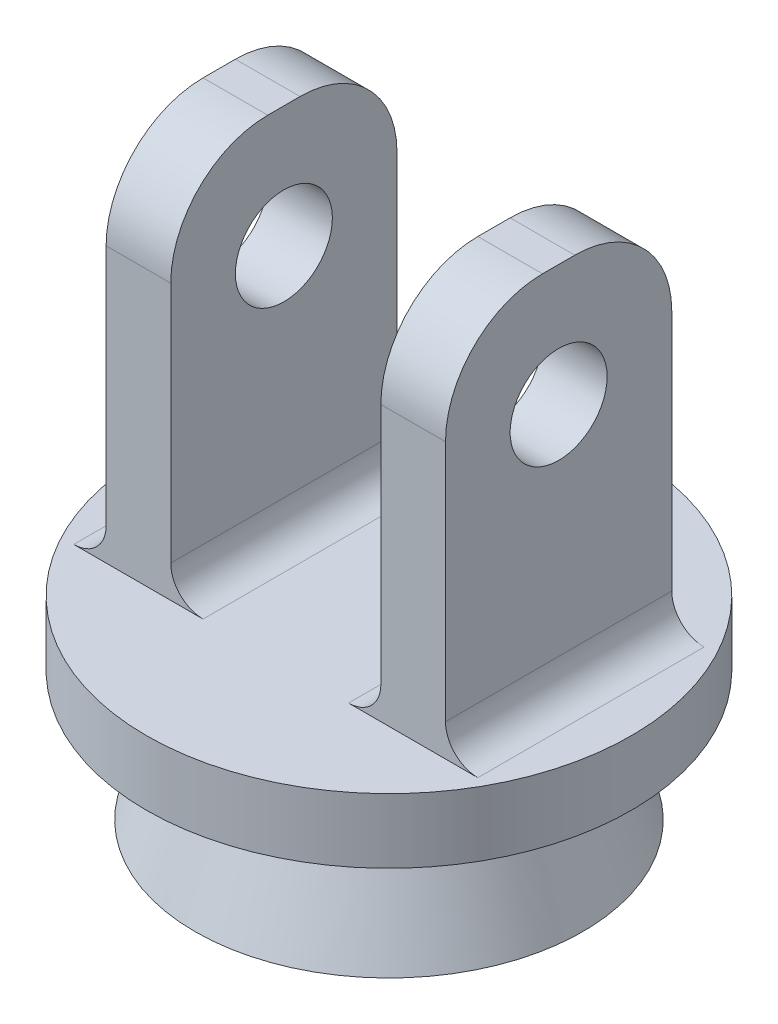
SolidWorks part; units mm, degrees
ref_plane "Front Plane" through (0, 0, 0) normal (0, 0, 1) x (1, 0, 0)
ref_plane "Top Plane" through (0, 0, 0) normal (0, 1, 0) x (1, 0, 0)
ref_plane "Right Plane" through (0, 0, 0) normal (1, 0, 0) x (0, 0, -1)
sketch "Sketch1" plane through (0, 0, 0) normal (0, 1, 0) x (1, 0, 0)
  circle A0 centre (0, 0) radius 152.4
  dimension "D1" = 304.8
extrude "Boss-Extrude1" add sketch "Sketch1" along normal blind 101.6 draft 20
sketch "Sketch2" plane through (0, 101.6, 0) normal (0, 1, 0) x (1, 0, 0)
  circle A0 centre (0, 0) radius 190.5
  dimension "D1" = 381
extrude "Boss-Extrude2" add sketch "Sketch2" along normal blind 50.8
sketch "Sketch3" plane through (0, 152.4, 0) normal (0, 1, 0) x (1, 0, 0)
  line L1 (-82.55, -88.9) -> (-133.35, -88.9)
  line L2 (-82.55, -88.9) -> (-82.55, 88.9)
  line L3 (-82.55, 88.9) -> (-133.35, 88.9)
  line L4 (-133.35, -88.9) -> (-133.35, 88.9)
  line L5 (-82.55, -88.9) -> (-133.35, 88.9) construction
  line L6 (-82.55, 88.9) -> (-133.35, -88.9) construction
  line L7 (133.35, -88.9) -> (82.55, -88.9)
  line L8 (133.35, -88.9) -> (133.35, 88.9)
  line L9 (133.35, 88.9) -> (82.55, 88.9)
  line L10 (82.55, -88.9) -> (82.55, 88.9)
  line L11 (133.35, -88.9) -> (82.55, 88.9) construction
  line L12 (133.35, 88.9) -> (82.55, -88.9) construction
  point P0 (-107.95, 0)
  point P5 (107.95, 0)
  dimension "D1" = 50.8
  dimension "D2" = 50.8
  dimension "D3" = 177.8
  dimension "D4" = 0
  dimension "D5" = 177.8
  dimension "D6" = 0
  dimension "D7" = 82.55
  dimension "D8" = 82.55
extrude "Boss-Extrude3" add sketch "Sketch3" along normal blind 292.1
fillet "Fillet1" radius 76.2 4 edges at (107.95, 444.5, -88.9) (107.95, 444.5, 88.9) (-107.95, 444.5, -88.9) (-107.95, 444.5, 88.9)
sketch "Sketch4" plane through (133.35, 0, 0) normal (1, 0, 0) x (0, 0, -1)
  line L0 (-88.9, 368.3) -> (-88.9, 152.4) construction
  line L2 (-12.7, 444.5) -> (12.7, 444.5) construction
  circle A0 centre (0, 349.25) radius 38.1
  dimension "D1" = 76.2
  dimension "D2" = 88.9
  dimension "D3" = 95.25
extrude "Cut-Extrude1" cut sketch "Sketch4" against normal up to surface (266.7 mm away) up to face at (-133.35, 326.9938, 0)
fillet "Fillet2" radius 25.4 4 edges at (133.35, 152.4, 0) (-133.35, 152.4, 0) (82.55, 152.4, 0) (-82.55, 152.4, 0)
